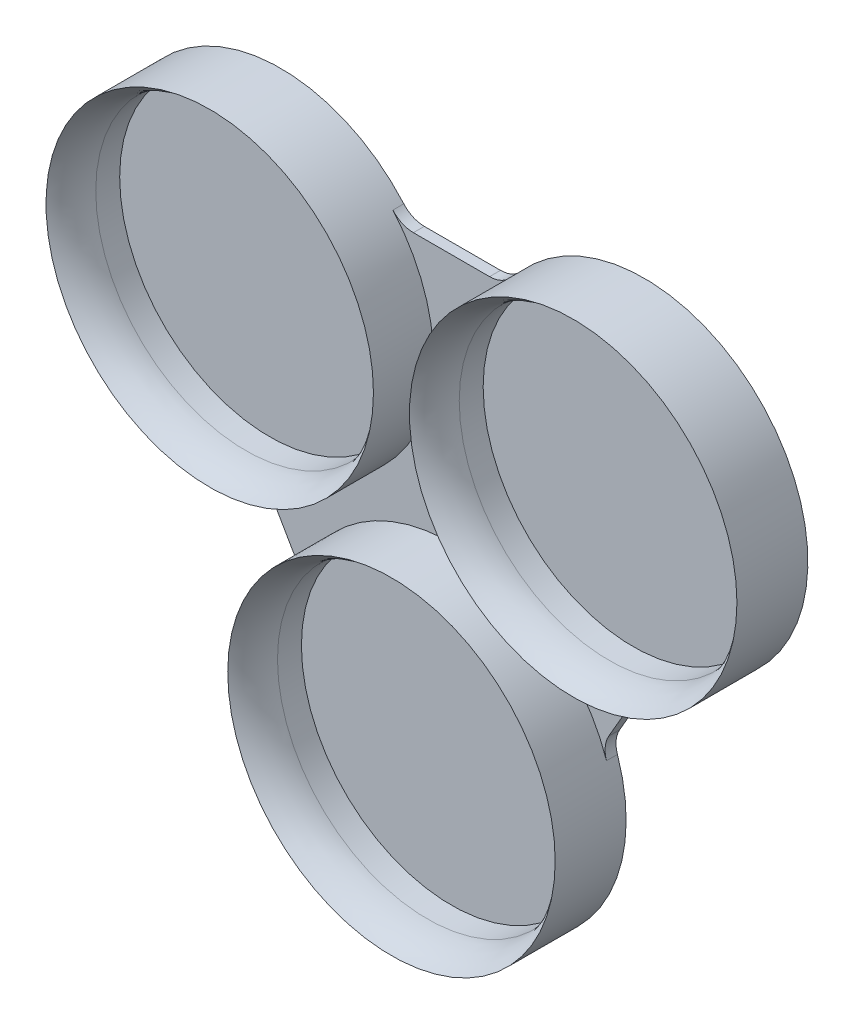
SolidWorks part; units mm, degrees
ref_plane "前视基准面" through (0, 0, 0) normal (0, 0, 1) x (1, 0, 0)
ref_plane "上视基准面" through (0, 0, 0) normal (0, 1, 0) x (1, 0, 0)
ref_plane "右视基准面" through (0, 0, 0) normal (1, 0, 0) x (0, 0, -1)
other "Configuration Table"
sketch "草图1" plane through (0, 0, 0) normal (0, 0, 1) x (1, 0, 0)
  line L0 (0, 0) -> (66.6, 0) construction
  line L1 (66.6, 0) -> (33.3, -57.6773) construction
  line L2 (33.3, -57.6773) -> (0, 0) construction
  circle A0 centre (0, 0) radius 27.5
  circle A1 centre (0, 0) radius 30
  circle A2 centre (66.6, 0) radius 30
  circle A3 centre (66.6, 0) radius 27.5
  circle A4 centre (33.3, -57.6773) radius 30
  circle A5 centre (33.3, -57.6773) radius 27.5
  dimension "D1" = 66.6
  dimension "D2" = 66.6
  dimension "D3" = 66.6
extrude "凸台-拉伸1" add sketch "草图1" along normal blind 13
sketch "草图2" plane through (0, 0, 0) normal (0, 0, 1) x (1, 0, 0)
  line L4 (26.3199, 18.0708) -> (40.2801, 18.0708)
  line L6 (69.0899, -31.8291) -> (62.1097, -43.919)
  line L8 (4.4903, -43.919) -> (-2.4899, -31.8291)
  arc A10 (22.5599, 19.775) -> (-5.8457, -29.425) centre (0, 0) ccw
  arc A11 (72.4457, -29.425) -> (44.0401, 19.775) centre (66.6, 0) ccw
  arc A12 (4.8944, -48.0273) -> (61.7056, -48.0273) centre (33.3, -57.6773) ccw
  arc A14 (4.8944, -48.0273) -> (4.4903, -43.919) centre (0.1601, -46.419) ccw
  arc A16 (-2.4899, -31.8291) -> (-5.8457, -29.425) centre (-6.82, -34.3291) ccw
  arc A17 (62.1097, -43.919) -> (61.7056, -48.0273) centre (66.4399, -46.419) ccw
  arc A18 (72.4457, -29.425) -> (69.0899, -31.8291) centre (73.42, -34.3291) ccw
  arc A19 (40.2801, 18.0708) -> (44.0401, 19.775) centre (40.2801, 23.0708) ccw
  arc A20 (26.3199, 18.0708) -> (22.5599, 19.775) centre (26.3199, 23.0708) cw
  dimension "D1" = 5
extrude "凸台-拉伸2" add sketch "草图2" along normal blind 2
sketch "草图3" plane through (0, 0, 0) normal (0, 0, 1) x (1, 0, 0)
  circle A0 centre (33.3, -57.6773) radius 27.5 construction
  circle A1 centre (66.6, 0) radius 27.5 construction
  circle A4 centre (33.3, -19.2258) radius 38.4515 construction
  circle A5 centre (33.3, -19.2258) radius 1.4
  circle A6 centre (33.3, -19.2258) radius 7 construction
  circle A7 centre (33.3, -12.2258) radius 1.65 construction
  circle A8 centre (40.3, -19.2258) radius 1.65 construction
  circle A9 centre (33.3, -26.2258) radius 1.65 construction
  circle A10 centre (26.3, -19.2258) radius 1.65 construction
  dimension "D1" = 14
  dimension "D2" = 2.8
  dimension "D3" = 3.3
  dimension "D4" = 14
extrude "切除-拉伸5" cut sketch "草图3" along normal through all
fillet "圆角1" radius 10 3 edges at (94.1, 0, 13) (27.5, 0, 13) (60.8, -57.6773, 13)
sketch "草图4" plane through (0, 0, 0) normal (0, 0, -1) x (-1, 0, 0)
  circle A0 centre (-33.3, -19.2258) radius 23.8475
sketch "草图5" plane through (0, 0, 0) normal (0, 0, -1) x (-1, 0, 0)
  circle A0 centre (-33.3, -19.2258) radius 10.5
  circle A1 centre (-33.3, -19.2258) radius 12.5
  dimension "D1" = 25
  dimension "D2" = 21
extrude "凸台-拉伸3" add sketch "草图5" along normal blind 7
sketch "草图6" plane through (0, 0, 0) normal (0, 0, -1) x (-1, 0, 0)
  line L0 (-63.7457, -19.2258) -> (9.4641, -19.2258) construction
  line L1 (-34.9033, -16.0585) -> (-43.5188, -16.8122)
  line L2 (-33.3, 23.5748) -> (-33.3, -99.3646) construction
  line L3 (-34.9033, -22.3931) -> (-43.5188, -21.6393)
  line L4 (-31.6967, -22.3931) -> (-23.0812, -21.6393)
  line L5 (-31.6967, -16.0585) -> (-23.0812, -16.8122)
  arc A0 (-34.9033, -22.3931) -> (-31.6967, -22.3931) centre (-33.3, -19.2258) ccw
  circle A1 centre (-33.3, -19.2258) radius 10.5 construction
  arc A3 (-43.5188, -21.6393) -> (-23.0812, -21.6393) centre (-33.3, -19.2258) ccw
  arc A4 (-31.6967, -16.0585) -> (-34.9033, -16.0585) centre (-33.3, -19.2258) ccw
  arc A5 (-23.0812, -16.8122) -> (-43.5188, -16.8122) centre (-33.3, -19.2258) ccw
  point P11 (-34.9033, -16.0585)
  dimension "D1" = 7.1
  dimension "D2" = 175
extrude "凸台-拉伸4" add sketch "草图6" along normal blind 2
